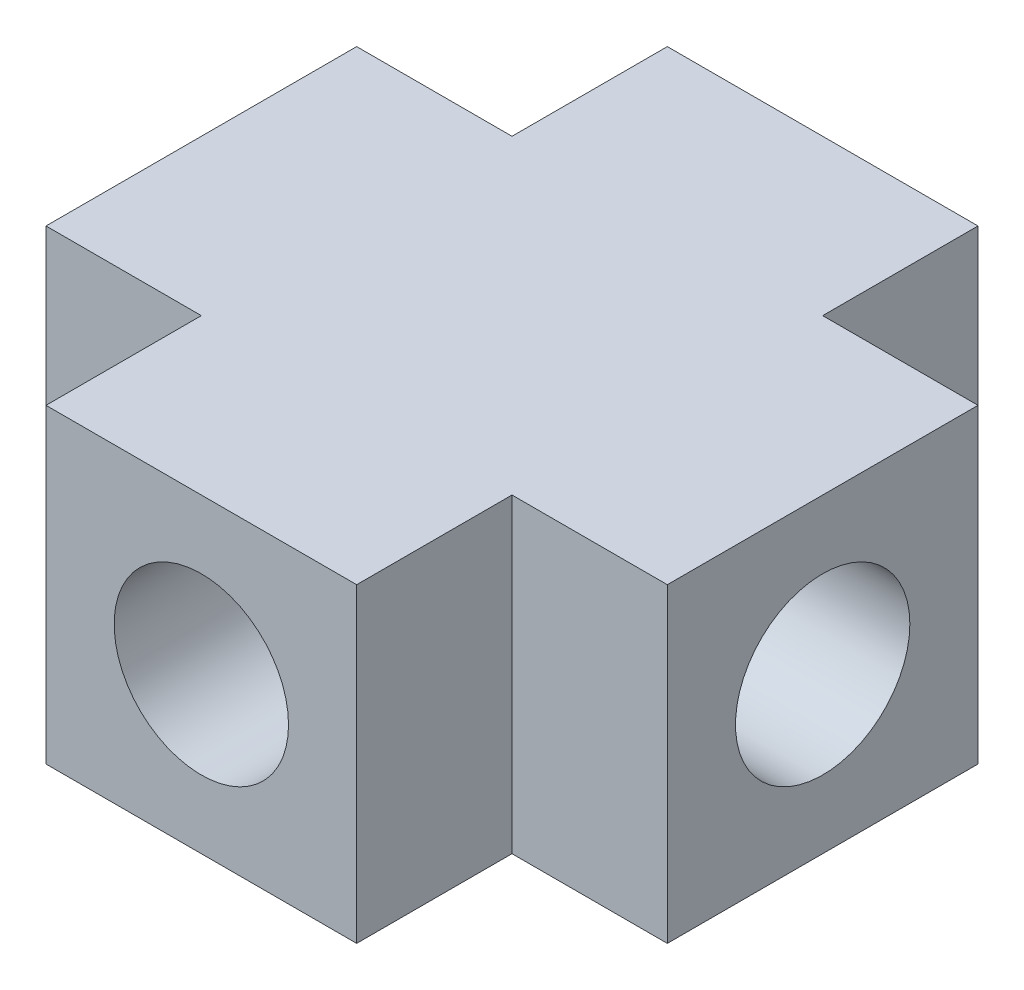
SolidWorks part; units mm, degrees
material "ABS"
ref_plane "Front Plane" through (0, 0, 0) normal (0, 0, 1) x (1, 0, 0)
ref_plane "Top Plane" through (0, 0, 0) normal (0, 1, 0) x (1, 0, 0)
ref_plane "Right Plane" through (0, 0, 0) normal (1, 0, 0) x (0, 0, -1)
sketch "Sketch1" plane through (0, 0, 0) normal (0, 1, 0) x (1, 0, 0)
  line L1 (-10, -5) -> (10, -5)
  line L2 (-10, -5) -> (-10, 5)
  line L3 (-10, 5) -> (10, 5)
  line L4 (10, -5) -> (10, 5)
  line L5 (-10, -5) -> (10, 5) construction
  line L6 (-10, 5) -> (10, -5) construction
  line L7 (-5, -10) -> (5, -10)
  line L8 (-5, -10) -> (-5, 10)
  line L9 (-5, 10) -> (5, 10)
  line L10 (5, -10) -> (5, 10)
  line L11 (-5, -10) -> (5, 10) construction
  line L12 (-5, 10) -> (5, -10) construction
  point P0 (0, 0)
  point P6 (0, 0)
  dimension "D1" = 10
  dimension "D2" = 20
extrude "Boss-Extrude1" add sketch "Sketch1" along normal mid plane 10 contours L7 L10 L1 L8 | L1 L10 L3 L8 | L1 L8 L3 L2 | L10 L1 L4 L3 | L3 L10 L9 L8 region at (-7.5, 0, 0) region at (0, 0, 0) region at (0, 0, 7.5) region at (7.5, 0, 0) region at (0, 0, -7.5)
sketch "Sketch2" plane through (0, 0, 10) normal (0, 0, 1) x (1, 0, 0)
  line L0 (-5, -5) -> (5, 5) construction
  line L1 (-5, 5) -> (5, -5) construction
  line L4 (-5, -5) -> (5, -5)
  line L5 (5, -5) -> (5, 5)
  line L6 (5, 5) -> (-5, 5)
  line L7 (-5, 5) -> (-5, -5)
  line L8 (-5, -5) -> (5, -5) construction
  line L9 (5, -5) -> (5, 5) construction
  line L10 (5, 5) -> (-5, 5) construction
  line L11 (-5, 5) -> (-5, -5) construction
  circle A0 centre (0, 0) radius 2.8067
  dimension "D2" = 5.6134
  dimension "D1" = 0
extrude "Cut-Extrude1" cut sketch "Sketch2" against normal blind 5
ref_axis "Axis1" through (0, 0, 0) along (0, 1, 0)
pattern_circular "CirPattern1" count 4 over 360 about axis through (0, 0, 0) along (0, 1, 0) of "Cut-Extrude1"
